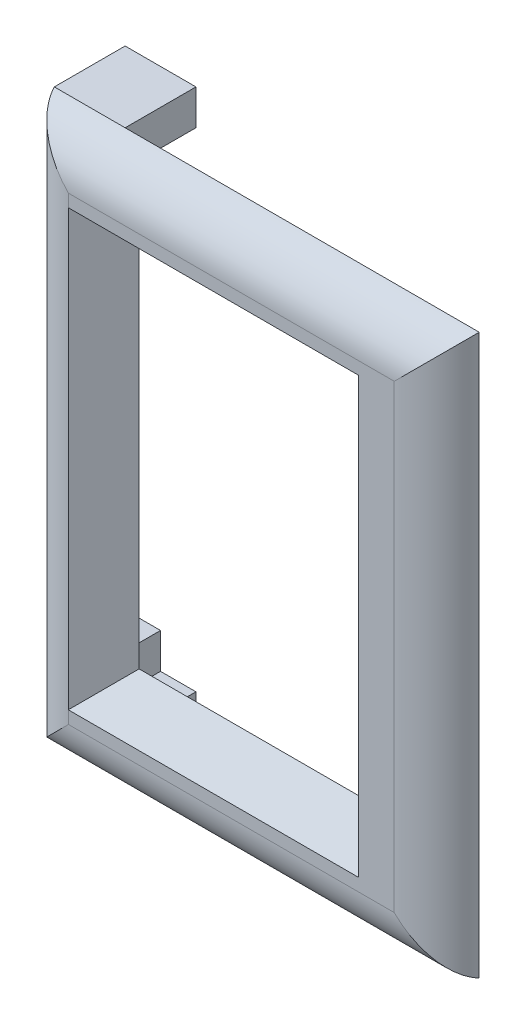
SolidWorks part; units mm, degrees
ref_plane "Front Plane" through (0, 0, 0) normal (0, 0, 1) x (1, 0, 0)
ref_plane "Top Plane" through (0, 0, 0) normal (0, 1, 0) x (1, 0, 0)
ref_plane "Right Plane" through (0, 0, 0) normal (1, 0, 0) x (0, 0, -1)
sketch "Sketch1" plane through (0, 0, 0) normal (0, 0, 1) x (1, 0, 0)
  line L0 (6.4876, 12.35) -> (23.4876, -12.35) construction
  line L1 (23.4876, 12.35) -> (23.4876, -12.35) construction
  line L2 (23.4876, -12.35) -> (20.9876, -12.35) construction
  line L3 (23.4876, 12.3498) -> (6.5124, -12.35) construction
  line L4 (6.4876, -12.35) -> (20.9876, -12.35) construction
  line L5 (0, 35.2425) -> (0, 19.8427) construction
  line L6 (0, 19.7425) -> (30, 19.7425)
  line L7 (0, 19.7425) -> (0, -19.7427)
  line L8 (0, -19.7427) -> (30, -19.7427)
  line L9 (30, 19.7425) -> (30, -19.7427)
  line L10 (0, 19.7425) -> (30, -19.7427) construction
  line L11 (0, -19.7427) -> (30, 19.7425) construction
  point P7 (15, -0.0001)
  point P18 (15, -0.0001)
extrude "Boss-Extrude1" add sketch "Sketch1" along normal blind 2.5
sketch "Sketch2" plane through (0, 0, 2.5) normal (0, 0, 1) x (1, 0, 0)
  line L1 (6.4876, 12.35) -> (20.9876, 12.35)
  line L2 (6.4876, 12.35) -> (6.4876, -12.35)
  line L3 (6.4876, -12.35) -> (20.9876, -12.35)
  line L4 (20.9876, 12.35) -> (20.9876, -12.35)
  line L5 (6.4876, 12.35) -> (20.9876, -12.35) construction
  line L6 (6.4876, -12.35) -> (20.9876, 12.35) construction
  point P4 (13.7376, 0)
extrude "Cut-Extrude1" cut sketch "Sketch2" against normal through all
chamfer "Chamfer2" distance 3 angle 45 4 edges at (13.7376, -12.35, 2.5) (20.9876, 0, 2.5) (13.7376, 12.35, 2.5) (6.4876, 0, 2.5)
fillet "Fillet5" radius 3.7 4 edges at (15, 19.7425, 2.5) (15, -19.7427, 2.5) (0, -0.0001, 2.5) (30, -0.0001, 2.5)
sketch "Sketch5" plane through (0, 0, 0) normal (0, 0, -1) x (-1, 0, 0)
  line L0 (-2.4876, 0) -> (-4.0276, 0) construction
  line L1 (0, -19.7427) -> (-5, -19.7427)
  line L2 (0, -19.7427) -> (0, -17.2427)
  line L4 (-5, -19.7427) -> (-5, -17.2427)
  line L5 (0, -19.7427) -> (-5, -17.2427) construction
  line L6 (0, -17.2427) -> (-5, -19.7427) construction
  line L7 (0, -19.7427) -> (-2.5, -19.7427)
  line L8 (0, -19.7427) -> (0, -14.7427)
  line L9 (0, -14.7427) -> (-2.5, -14.7427)
  line L11 (0, -19.7427) -> (-2.5, -14.7427) construction
  line L12 (0, -14.7427) -> (-2.5, -19.7427) construction
  line L13 (-2.5, 17.2427) -> (-5, 17.2427)
  line L14 (-5, 19.7427) -> (-5, 17.2427)
  line L15 (0, 19.7427) -> (-5, 19.7427)
  line L16 (-2.5, 17.2427) -> (-2.5, 14.7427)
  line L17 (0, 14.7427) -> (-2.5, 14.7427)
  line L18 (0, 19.7427) -> (0, 14.7427)
  line L19 (-2.5, -17.2427) -> (-2.5, -14.7427)
  line L20 (-2.5, -17.2427) -> (-5, -17.2427)
  line L21 (-15.0876, -12.7) -> (-15.0876, 12.7) construction
  line L22 (-28.1876, -12.7) -> (-1.9876, -12.7) construction
  line L23 (-1.9876, 12.7) -> (-28.1876, 12.7) construction
  point P4 (-2.5, -18.4927)
  point P9 (-1.25, -17.2427)
  line M10 (-30, -19.7427) -> (0, -19.7427)
  line M11 (0, -19.7427) -> (0, 19.7425)
  line M12 (0, 19.7425) -> (-30, 19.7425)
  dimension "D1" = 5
  dimension "D2" = 2.5
extrude "Boss-Extrude2" add sketch "Sketch5" along normal blind 5 contours L17 L14 L13 L16 M11 M12 | L19 L20 L4 L1 L9 M10 M11
sketch "Sketch6" plane through (0, 0, -2.5) normal (0, 0, -1) x (-1, 0, 0)
  line L0 (-15.0876, -12.7) -> (-15.0876, 12.7) construction
  line L1 (-5.9876, -12.7) -> (-24.1876, -12.7) construction
  line L2 (-5.9876, 12.7) -> (-16.4222, 12.7) construction
